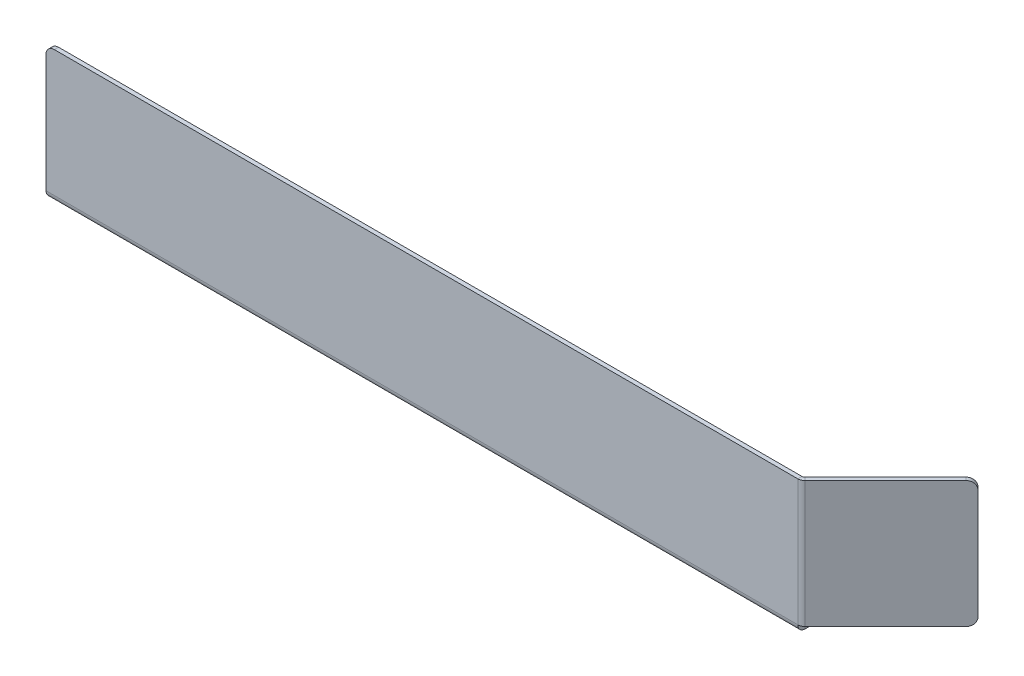
SolidWorks part; units mm, degrees
note: The reader was unsure of these and kept them because the rebuilt part matched: flange length of "Edge-Flange1", "Edge-Flange2".
ref_plane "Front Plane" through (0, 0, 0) normal (0, 0, 1) x (1, 0, 0)
ref_plane "Top Plane" through (0, 0, 0) normal (0, 1, 0) x (1, 0, 0)
ref_plane "Right Plane" through (0, 0, 0) normal (1, 0, 0) x (0, 0, -1)
sketch "Sketch2" plane through (0, 0, 0) normal (0, 0, 1) x (1, 0, 0)
  line L1 (0, 0) -> (-180, 0)
  line L2 (0, 0) -> (0, 32)
  line L3 (0, 32) -> (-180, 32)
  line L4 (-180, 0) -> (-180, 32)
  dimension "D1" = 32
  dimension "D2" = 180
base flange "Base-Flange1" sketch "Sketch2" thickness 1 reverse thickness direction no parameters "D1"=0.7366
ref_plane "Plane1" through (0, 0, 0) normal (1, 0, 0) x (0, 0, -1)
edge flange "Edge-Flange1" sketch "Sketch10" flange angle 90 flange length 18 flange position material inside bend radius 0.7366 thickness 1 parameters "D6"=10
sketch "Sketch10" plane through (0, 0, -1) normal (0, 1, 0) x (1, 0, 0)
  line L0 (0, 0) -> (-180, 0) construction
  line L2 (-180, 0) -> (-180, 17)
  line L3 (-180, 17) -> (0, 17)
  line L4 (0, 17) -> (0, 0)
  line L7 (0, 0) -> (-180, 0)
bend "EdgeBend1" bend radius 0.7366 bend angle 90 parameters "D5"=1
edge flange "Edge-Flange2" sketch "Sketch14" flange angle 135 flange length 30 flange position bend outside bend radius 0.7366 thickness 1 parameters "D6"=10
sketch "Sketch14" plane through (0, 0, -1) normal (-0.7071, 0, -0.7071) x (0, 1, 0)
  line L0 (32, 0) -> (1.7366, 0) construction
  line L2 (1.7366, 0) -> (1.7366, 29.5858)
  line L3 (1.7366, 29.5858) -> (32, 29.5858)
  line L4 (32, 29.5858) -> (32, 0)
  line L10 (32, 0) -> (1.7366, 0)
bend "EdgeBend2" bend radius 0.7366 bend angle 45 parameters "D5"=2
fillet "Fillet1" radius 2 5 edges at (0, 0.5, -18) (-180, 0.5, -18) (-180, 32, -0.5) (21.579, 1.7366, -21.5668) (21.579, 32, -21.5668)
sketch "Bend-Lines1" [suppressed] plane through (0, 0, 0) normal (0, 1, 0) x (1, 0, 0)
sketch "Bounding-Box1" [suppressed] plane through (0, 0, 0) normal (0, 1, 0) x (1, 0, 0)
sheet metal parameters "Sheet-Metal1" thickness 1 parameters "D1"=0.7366
flat pattern "Flat-Pattern1" [suppressed]
sketch "Bend-Lines2" plane through (0, 0, 0) normal (0, 1, 0) x (1, 0, 0)
sketch3d "Bounding-Box2" [suppressed]
  line L0 (64.5873, 0, 0) -> (0, 0, 0) construction
  line L1 (64.5873, 22.0538, 0) -> (0, 22.0538, 0) construction
  line L2 (64.5873, 0, 0) -> (64.5873, 22.0538, 0) construction
  line L3 (0, 0, 0) -> (0, 22.0538, 0) construction
sheet metal parameters "Sheet-Metal2" thickness 1 parameters "D1"=0.7366
flat pattern "Flat-Pattern1"
sketch "Bend-Lines2" plane through (0, 0, 0) normal (0, 0, 1) x (1, 0, 0)
  line L0 (-64.5873, 0.7654) -> (0, 0.7654) construction
  line L1 (-64.5873, 0.7654) -> (0, 0.7654) construction
sketch3d "Bounding-Box2" [suppressed]
  line L0 (-64.5873, -7.4692, 0) -> (0, -7.4692, 0) construction
  line L1 (-64.5873, 22.0538, 0) -> (0, 22.0538, 0) construction
  line L2 (-64.5873, -7.4692, 0) -> (-64.5873, 22.0538, 0) construction
  line L3 (0, -7.4692, 0) -> (0, 22.0538, 0) construction
bend of the flat pattern "Flatten-<EdgeBend1>1"
sheet metal parameters "Sheet-Metal3" thickness 1 parameters "D1"=0.7366
flat pattern "Flat-Pattern1"
sketch "Bend-Lines2" plane through (0, 0, 0) normal (0, 0, 1) x (1, 0, 0)
  line L0 (-180, 0.7654) -> (0, 0.7654) construction
  line L1 (-180, 0.7654) -> (0, 0.7654) construction
  line L2 (0.4856, 1.7366) -> (0.4856, 30) construction
  line L3 (0.4856, 1.7366) -> (0.4856, 30) construction
sketch3d "Bounding-Box2" [suppressed]
  line L0 (-180, -16.4692, 0) -> (30.2519, -16.4692, 0) construction
  line L1 (-180, 30, 0) -> (30.2519, 30, 0) construction
  line L2 (-180, -16.4692, 0) -> (-180, 30, 0) construction
  line L3 (30.2519, -16.4692, 0) -> (30.2519, 30, 0) construction
bend of the flat pattern "Flatten-<EdgeBend2>1"
bend of the flat pattern "Flatten-<EdgeBend1>1"
